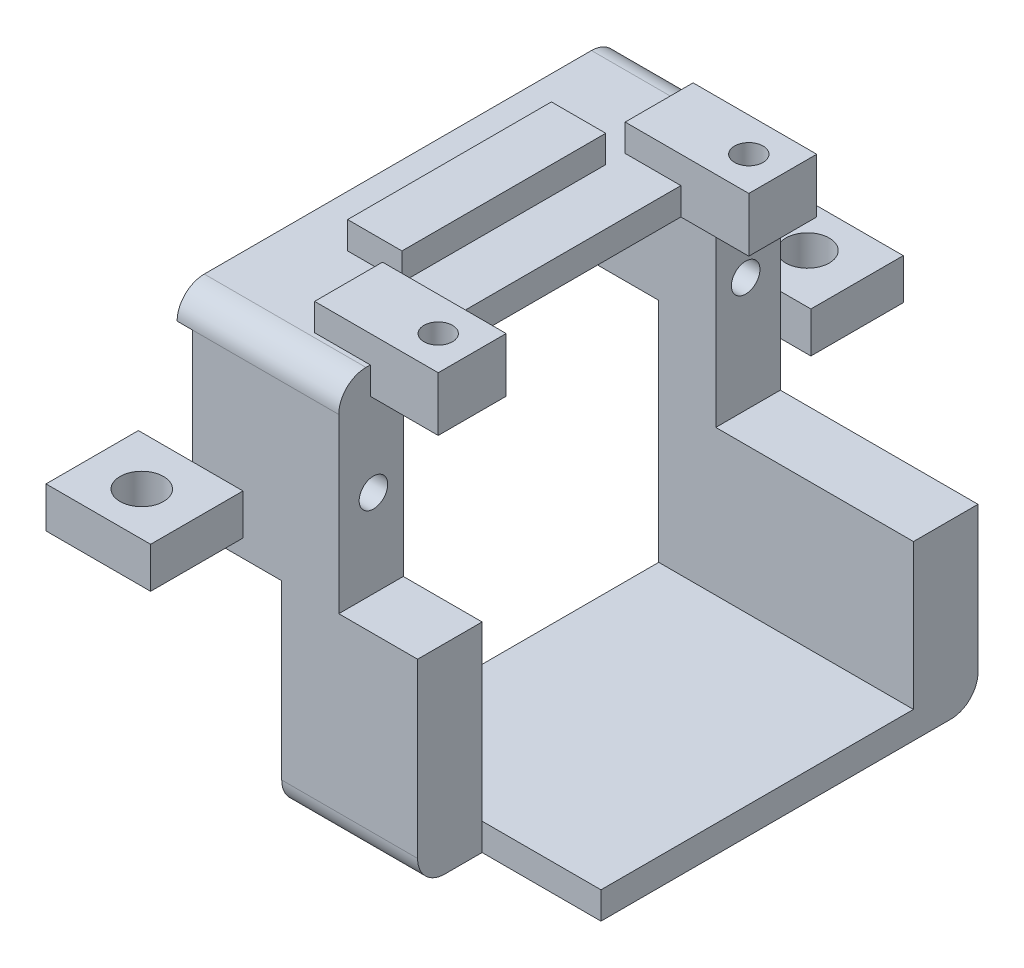
SolidWorks part; units mm, degrees
ref_plane "Front Plane" through (0, 0, 0) normal (0, 0, 1) x (1, 0, 0)
ref_plane "Top Plane" through (0, 0, 0) normal (0, 1, 0) x (1, 0, 0)
ref_plane "Right Plane" through (0, 0, 0) normal (1, 0, 0) x (0, 0, -1)
sketch "Sketch1" plane through (0, 0, 0) normal (0, 1, 0) x (1, 0, 0)
  line L0 (-1.1, 16.25) -> (-1.1, 11.5)
  line L1 (-17.65, -16.25) -> (17.65, -16.25)
  line L2 (-17.65, -16.25) -> (-17.65, 16.25)
  line L3 (-17.65, 16.25) -> (17.65, 16.25)
  line L4 (17.65, -16.25) -> (17.65, 16.25)
  line L5 (-17.65, -16.25) -> (17.65, 16.25) construction
  line L6 (-17.65, 16.25) -> (17.65, -16.25) construction
  line L7 (-1.1, 11.5) -> (17.65, 11.5)
  line L8 (-1.1, -16.25) -> (-1.1, -11.5)
  line L9 (-1.1, -11.5) -> (17.65, -11.5)
  line L10 (-1.1, 11.5) -> (-1.1, -11.5) construction
  line L11 (8.9, -11.5) -> (8.9, -16.25)
  line L12 (-8.8, 16.25) -> (-8.8, 11.5)
  line L13 (-8.8, 11.5) -> (-3.8, 11.5)
  line L14 (-3.8, 11.5) -> (-3.8, 16.25)
  line L15 (-3.8, -16.25) -> (-3.8, -11.5)
  line L16 (-3.8, -11.5) -> (-8.8, -11.5)
  line L17 (-8.8, -11.5) -> (-8.8, -16.25)
  line L18 (-8.8, 11.5) -> (-8.8, -11.5)
  line L19 (5.35, 16.25) -> (5.35, 23.05)
  line L20 (5.35, 23.05) -> (-2.35, 23.05)
  line L21 (-2.35, 23.05) -> (-2.35, 16.25)
  line L22 (-11.65, -16.25) -> (-11.65, -23.05)
  line L23 (-11.65, -23.05) -> (-3.95, -23.05)
  line L24 (-3.95, -23.05) -> (-3.95, -16.25)
  line L25 (9.53, -16.25) -> (9.53, -23.05)
  line L26 (9.53, -23.05) -> (17.23, -23.05)
  line L27 (17.23, -23.05) -> (17.23, -16.25)
  line L28 (-1.1, 11.5) -> (-1.1, -11.5)
  circle A0 centre (1.5, 19.85) radius 1.6
  circle A1 centre (13.38, -19.85) radius 1.6
  circle A2 centre (-7.8, -19.85) radius 1.6
  point P0 (0, 0)
  point P11 (-1.1, 0)
  point P31 (1.5, 23.05)
  point P45 (-7.8, -23.05)
  point P48 (13.38, -23.05)
  dimension "D11" = 3.2
  dimension "D18" = 3.2
  dimension "D19" = 3.2
  dimension "D1" = 32.5
  dimension "D2" = 23
  dimension "D3" = 8.75
  dimension "D4" = 10
  dimension "D5" = 16.55
  dimension "D6" = 2.7
  dimension "D7" = 5
  dimension "D8" = 1.5
  dimension "D9" = 7.7
  dimension "D10" = 6.8
  dimension "D12" = 9.85
  dimension "D13" = 31.03
  dimension "D14" = 7.7
  dimension "D15" = 19.85
  dimension "D16" = 7.7
  dimension "D17" = 6.8
  dimension "D20" = 19.85
extrude "Boss-Extrude1" add sketch "Sketch1" against normal blind 2 contours L7 L28 L9 L4 | L0 L7 L4 L3 | L11 L9 L8 L1 region at (8.275, 0, -13.875) region at (8.275, 0, 0) region at (3.9, 0, 13.875)
extrude "Boss-Extrude2" add sketch "Sketch1<3>" along normal blind 12.7 contours L0 L7 L4 L3 | L11 L9 L8 L1 region at (8.275, 0, -13.875) region at (3.9, 0, 13.875)
sketch "Sketch1<3>" plane through (0, 0, 0) normal (0, 1, 0) x (1, 0, 0) same geometry as "Sketch1"
sketch "Sketch3" plane through (0, 0, 0) normal (0, 1, 0) x (1, 0, 0)
  line L0 (3.1, 16.25) -> (3.1, 11.5)
  line L1 (-17.65, 16.25) -> (17.65, 16.25) construction
  line L2 (-1.1, 11.5) -> (17.65, 11.5) construction
  line L3 (3.1, 11.5) -> (-17.65, 11.5)
  line L4 (-17.65, -16.25) -> (-17.65, 16.25) construction
  line L5 (3.1, -16.25) -> (3.1, -11.5)
  line L6 (-17.65, -16.25) -> (17.65, -16.25) construction
  line L7 (-1.1, -11.5) -> (17.65, -11.5) construction
  line L8 (3.1, -11.5) -> (-17.65, -11.5)
  line L9 (3.1, 11.5) -> (3.1, -11.5)
  line L10 (-7.65, -11.5) -> (-7.65, -16.275)
  line L11 (3.1, 16.25) -> (-17.65, 16.25)
  line L12 (-17.65, 16.25) -> (-17.65, 11.5)
  line L13 (-17.65, -11.5) -> (-17.65, -16.25)
  line L14 (-17.65, -16.25) -> (3.1, -16.25)
  line L15 (-8.8, 11.5) -> (-8.8, -11.5)
  line L16 (-8.8, 11.5) -> (-8.8, 16.25)
  line L17 (-8.8, -11.5) -> (-8.8, -16.25)
  dimension "D1" = 20.75
  dimension "D2" = 10
extrude "Boss-Extrude3" add sketch "Sketch3" along normal blind 12.7 from surface contours L11 L12 L3 L0 | L10 L14 L5 L8 region at (-2.85, 0, -13.875) region at (-2.275, 0, 13.875) starting at face at (8.275, 12.7, -13.875)
extrude "Boss-Extrude4" add sketch "Sketch3<3>" along normal blind 2 from surface contours L16 L3 L0 L11 | L3 L15 L8 L9 | L10 L14 L5 L8 | L8 L17 L14 L10 region at (-2.85, 0, -13.875) region at (-2.85, 0, 0) region at (-2.275, 0, 13.875) region at (-8.225, 0, 13.875) starting at face at (-2.275, 25.4, 13.875)
sketch "Sketch3<3>" plane through (0, 0, 0) normal (0, 1, 0) x (1, 0, 0) same geometry as "Sketch3"
sketch "Sketch2" plane through (0, 0, 0) normal (1, 0, 0) x (0, 0, -1)
  line L0 (13.7, 6.45) -> (-13.7, 6.45) construction
  line L1 (-13.7, 19.15) -> (13.7, 19.15) construction
  circle A0 centre (13.7, 6.45) radius 1.05
  circle A1 centre (-13.7, 6.45) radius 1.05
  circle A2 centre (-13.7, 19.15) radius 1.05
  circle A3 centre (13.7, 19.15) radius 1.05
  point P4 (0, 6.45)
  dimension "D1" = 2.1
  dimension "D2" = 2.1
  dimension "D6" = 2.1
  dimension "D7" = 2.1
  dimension "D3" = 27.4
  dimension "D4" = 6.45
  dimension "D5" = 6.45
extrude "Cut-Extrude1" cut sketch "Sketch2" along normal blind 8 from surface contours A1 | A0 region at (0, 6.45, -13.7) region at (0, 6.45, 13.7) starting at face at (-1.1, 5.85, 0)
extrude "Cut-Extrude2" cut sketch "Sketch2<3>" against normal blind 8 from surface contours A3 | A2 region at (0, 19.15, 13.7) region at (0, 19.15, -13.7) starting at face at (3.1, 19.55, 0)
sketch "Sketch2<3>" plane through (0, 0, 0) normal (1, 0, 0) x (0, 0, -1) same geometry as "Sketch2"
extrude "Boss-Extrude5" add sketch "Sketch1<4>" against normal blind 3 from offset 17 contours L20 L21 L3 L19 A0 | L23 L24 L1 L22 A2 region at (-1.725, 0, -16.3527) region at (-4.0527, 0, 19.65)
sketch "Sketch1<4>" plane through (0, 0, 0) normal (0, 1, 0) x (1, 0, 0) same geometry as "Sketch1"
fillet "Fillet1" radius 2 4 edges at (3.9, -2, 16.25) (-2.85, 27.4, 16.25) (8.275, -2, -16.25) (-2.85, 27.4, -16.25)
sketch "Sketch5" plane through (0, 0, 0) normal (0, 1, 0) x (1, 0, 0)
  line L1 (17.65, 16.25) -> (3.1, 16.25)
  line L2 (17.65, 16.25) -> (17.65, 11.5)
  line L3 (17.65, 11.5) -> (3.1, 11.5)
  line L4 (3.1, 16.25) -> (3.1, 11.5)
extrude "Cut-Extrude3" cut sketch "Sketch5" against normal blind 2 from surface starting at face at (10.375, 12.7, -13.875)
sketch "Sketch6" plane through (0, 0, 0) normal (0, 1, 0) x (1, 0, 0)
  line L1 (-8.8, 11.5) -> (-1.1, 11.5)
  line L2 (-8.8, 11.5) -> (-8.8, 16.25)
  line L3 (-8.8, 16.25) -> (-1.1, 16.25)
  line L4 (-1.1, 11.5) -> (-1.1, 16.25)
extrude "Cut-Extrude4" cut sketch "Sketch6" along normal blind 4 from surface starting at face at (-4.95, 12.7, -13.875)
sketch "Sketch7" plane through (0, 0, 0) normal (0, 1, 0) x (1, 0, 0)
  line L0 (5.6, 11.43) -> (5.6, -11.43) construction
  line L2 (3.1, 8.93) -> (8.1, 8.93)
  line L3 (3.1, 8.93) -> (3.1, 13.93)
  line L4 (3.1, 13.93) -> (8.1, 13.93)
  line L5 (8.1, 8.93) -> (8.1, 13.93)
  line L6 (3.1, 8.93) -> (8.1, 13.93) construction
  line L7 (3.1, 13.93) -> (8.1, 8.93) construction
  line L8 (-5, -7.5) -> (-1, -7.5)
  line L9 (3.1, -8.93) -> (8.1, -8.93)
  line L10 (3.1, -8.93) -> (3.1, -13.93)
  line L11 (3.1, -13.93) -> (8.1, -13.93)
  line L12 (8.1, -8.93) -> (8.1, -13.93)
  line L13 (3.1, -8.93) -> (8.1, -13.93) construction
  line L14 (3.1, -13.93) -> (8.1, -8.93) construction
  line L15 (-5, -7.5) -> (-5, 7.5)
  line L16 (3.1, 12.65) -> (3.1, 14.75) construction
  line L17 (-5, 7.5) -> (-1, 7.5)
  line L18 (-1, -7.5) -> (-1, 7.5)
  line L19 (-5, -7.5) -> (-1, 7.5) construction
  line L20 (-5, 7.5) -> (-1, -7.5) construction
  line L22 (3.1, -8.93) -> (-1, -8.93)
  line L23 (3.1, -8.93) -> (3.1, -13.93)
  line L24 (3.1, -13.93) -> (-1, -13.93)
  line L25 (-1, -8.93) -> (-1, -13.93)
  line L26 (3.1, 13.93) -> (-1, 13.93)
  line L27 (3.1, 13.93) -> (3.1, 8.93)
  line L28 (3.1, 8.93) -> (-1, 8.93)
  line L29 (-1, 13.93) -> (-1, 8.93)
  circle A0 centre (5.6, 11.43) radius 1.05
  circle A1 centre (5.6, -11.43) radius 1.05
  point P4 (5.6, 0)
  point P14 (-3, 0)
  dimension "D2" = 2.1
  dimension "D3" = 2.1
  dimension "D1" = 22.86
  dimension "D4" = 4
  dimension "D5" = 5
  dimension "D6" = 5
  dimension "D7" = 5
  dimension "D8" = 5
  dimension "D9" = 15
  dimension "D10" = 3
extrude "Boss-Extrude6" add sketch "Sketch7" along normal blind 2 and the other way blind 2 from surface contours L8 L18 L17 L15 | L26 L29 L18 L28 L3 | L2 L5 L4 L3 A0 | L18 L25 L24 L10 L22 | L12 L9 L10 L11 A1 region at (3.1707, 0, -11.43) region at (1.05, 0, -11.43) region at (-3, 0, 0) region at (5.6, 0, 9.0007) region at (1.05, 0, 11.43) starting at face at (-2.85, 27.4, 0)
